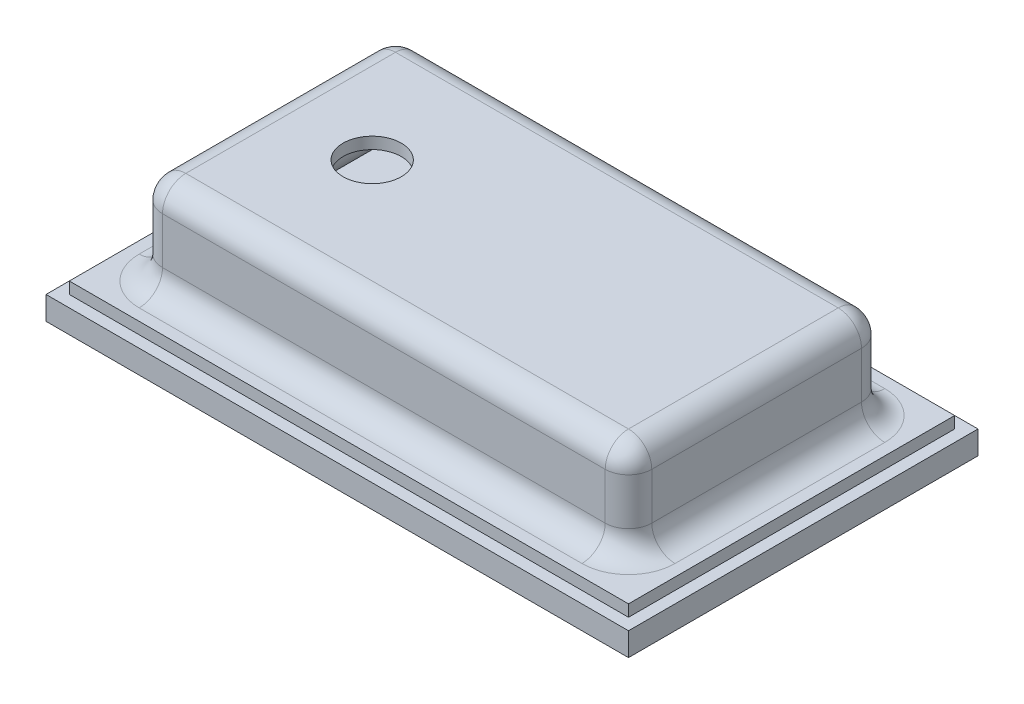
SolidWorks part; units mm, degrees
ref_plane "Front Plane" through (0, 0, 0) normal (0, 0, 1) x (1, 0, 0)
ref_plane "Top Plane" through (0, 0, 0) normal (0, 1, 0) x (1, 0, 0)
ref_plane "Right Plane" through (0, 0, 0) normal (1, 0, 0) x (0, 0, -1)
ref_plane "Plane1" through (0, 0.2, 0) normal (0, 1, 0) x (-1, 0, 0)
sketch "Sketch1" plane through (0, 0, 0) normal (0, 1, 0) x (1, 0, 0)
  line L0 (2.5, -1.5) -> (-2.5, 1.5) construction
  line L1 (-2.5, -1.5) -> (2.5, -1.5)
  line L2 (-2.5, -1.5) -> (-2.5, 1.5)
  line L3 (-2.5, 1.5) -> (2.5, 1.5)
  line L4 (2.5, -1.5) -> (2.5, 1.5)
  dimension "D1" = 3
  dimension "D2" = 5
sketch "Sketch2" plane through (0, 0.2, 0) normal (0, 1, 0) x (1, 0, 0)
  line L0 (2.4, -1.4) -> (-2.4, 1.4) construction
  line L1 (-2.4, 1.4) -> (2.4, 1.4)
  line L2 (-2.4, 1.4) -> (-2.4, -1.4)
  line L3 (-2.4, -1.4) -> (2.4, -1.4)
  line L4 (2.4, 1.4) -> (2.4, -1.4)
  dimension "D1" = 4.8
  dimension "D2" = 2.8
extrude "Boss-Extrude2" add sketch "Sketch2" along normal blind 0.1
sketch "Sketch3" plane through (0, 0.3, 0) normal (0, 1, 0) x (1, 0, 0)
  line L0 (2.1, -1.1) -> (-2.1, 1.1) construction
  line L1 (-2.1, 1.1) -> (2.1, 1.1)
  line L2 (-2.1, 1.1) -> (-2.1, -1.1)
  line L3 (-2.1, -1.1) -> (2.1, -1.1)
  line L4 (2.1, 1.1) -> (2.1, -1.1)
  line L5 (2.4, -1.4) -> (2.4, 1.4) construction
  line L6 (2.4, 1.4) -> (-2.4, 1.4) construction
  dimension "D1" = 0.3
  dimension "D2" = 0.3
extrude "Boss-Extrude3" add sketch "Sketch3" along normal blind 0.8
fillet "Fillet1" radius 0.2 12 edges at (-2.1, 0.3, 0) (-2.1, 0.7, -1.1) (0, 0.3, -1.1) (0, 1.1, -1.1) (-2.1, 1.1, 0) (2.1, 1.1, 0) (2.1, 0.7, -1.1) (2.1, 0.3, 0) (-2.1, 0.7, 1.1) (0, 1.1, 1.1) (2.1, 0.7, 1.1) (0, 0.3, 1.1)
shell "Shell3" thickness 0.1 removed face at (0, 0.2, 0)
extrude "Boss-Extrude4" add sketch "Sketch1" along normal blind 0.2
sketch "Sketch4" plane through (0, 1.1, 0) normal (0, 1, 0) x (1, 0, 0)
  line L0 (0, 0) -> (-1.2, 0) construction
  line L2 (-2.5, 1.5) -> (-2.5, -1.5) construction
  circle A0 centre (-1.2, 0) radius 0.25
  dimension "D1" = 0.5
  dimension "D2" = 1.3
extrude "Cut-Extrude1" cut sketch "Sketch4" against normal blind 0.2
